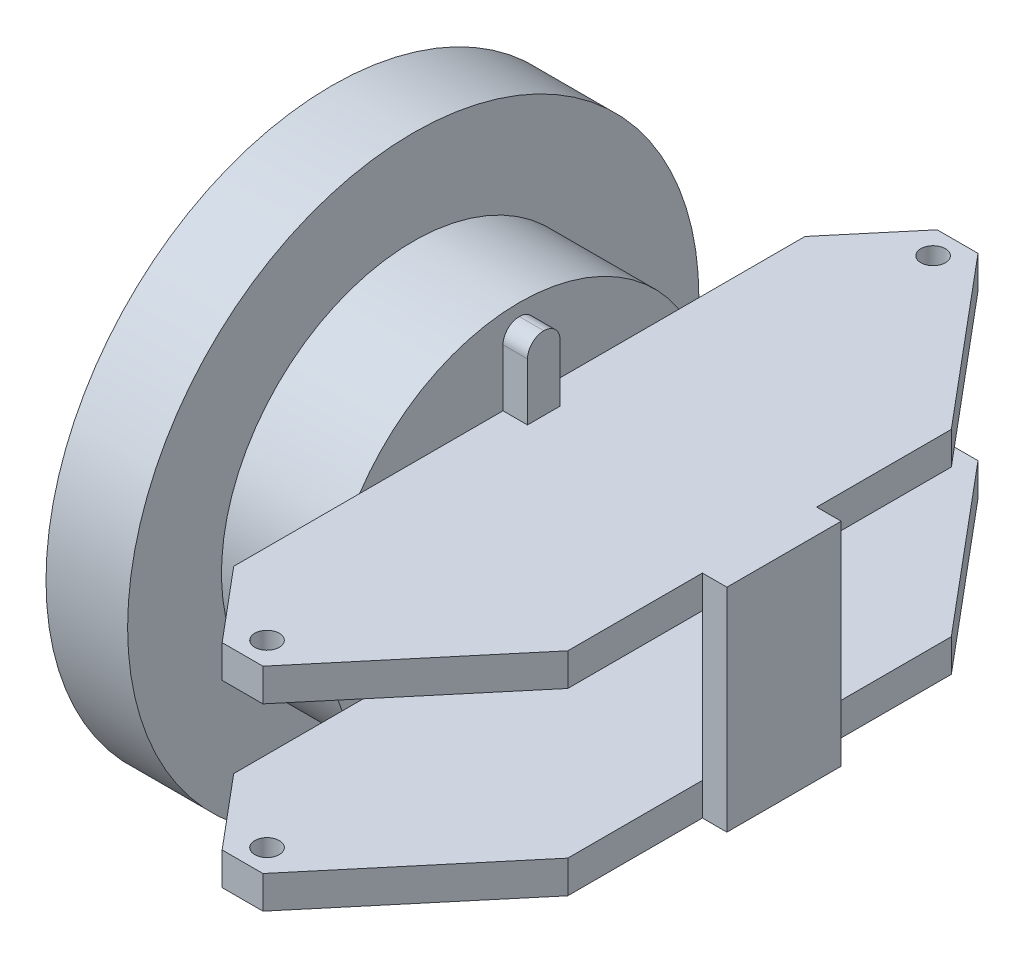
SolidWorks part; units mm, degrees
ref_plane "Front Plane" through (0, 0, 0) normal (0, 0, 1) x (1, 0, 0)
ref_plane "Top Plane" through (0, 0, 0) normal (0, 1, 0) x (1, 0, 0)
ref_plane "Right Plane" through (0, 0, 0) normal (1, 0, 0) x (0, 0, -1)
sketch "Sketch1" plane through (0, 0, 0) normal (1, 0, 0) x (0, 0, -1)
  circle A0 centre (0, 0) radius 35
  dimension "D1" = 70
extrude "Boss-Extrude1" add sketch "Sketch1" along normal blind 10
sketch "Sketch2" plane through (10, 0, 0) normal (1, 0, 0) x (0, 0, -1)
  circle A0 centre (0, 0) radius 23.5
  dimension "D1" = 47
extrude "Boss-Extrude2" add sketch "Sketch2" along normal blind 13
ref_plane "Plane2" through (0, 13, 0) normal (0, 1, 0) x (1, 0, 0)
sketch "Sketch3" plane through (0, 13, 0) normal (0, 1, 0) x (1, 0, 0)
  line L0 (23, 35) -> (23, -35)
  line L1 (23, -23.5) -> (23, 23.5) construction
  line L2 (23, -35) -> (30.3921, -43.8095)
  line L3 (30.3921, -43.8095) -> (35.3921, -43.8095)
  line L4 (35.3921, -43.8095) -> (46.1533, -43.8095) construction
  line L5 (35.3921, -43.8095) -> (52.4338, -23.5)
  line L6 (23, -23.5) -> (77.012, -23.5) construction
  line L7 (52.4338, -23.5) -> (52.4338, 23.5)
  line L8 (23, 0) -> (47.1697, 0) construction
  line L9 (30.3921, 43.8095) -> (35.3921, 43.8095)
  line L10 (23, 35) -> (30.3921, 43.8095)
  line L11 (35.3921, 43.8095) -> (52.4338, 23.5)
  line L12 (10, -23.5) -> (23, -23.5) construction
  point P16 (52.4338, 0)
  dimension "D1" = 35
  dimension "D2" = 11.5
  dimension "D3" = 40
  dimension "D4" = 5
  dimension "D5" = 50
extrude "Boss-Extrude3" add sketch "Sketch3" against normal blind 4
sketch "Sketch4" plane through (0, 13, 0) normal (0, 1, 0) x (1, 0, 0)
  line L0 (30.3921, -43.8095) -> (35.3921, -43.8095) construction
  circle A0 centre (32.8921, -40.8095) radius 1.5
  point P4 (32.8921, -43.8095)
  dimension "D1" = 3
  dimension "D2" = 3
extrude "Cut-Extrude1" cut sketch "Sketch4" against normal blind 4
mirror "Mirror1" about plane through (0, 0, 0) normal (0, 0, 1) of "Cut-Extrude1"
mirror "Mirror2" about plane through (0, 0, 0) normal (0, 1, 0) of "Mirror1", "Cut-Extrude1", "Boss-Extrude3"
sketch "Sketch5" plane through (23, 0, 0) normal (1, 0, 0) x (0, 0, -1)
  line L0 (0, 13) -> (0, 23.5) construction
  line L1 (19.5768, 13) -> (-19.5768, 13) construction
  line L2 (0, 13) -> (-2, 13)
  line L3 (-23.5, 13) -> (23.5, 13) construction
  line L4 (-2, 13) -> (-2, 22)
  line L5 (-2, 22) -> (2, 22)
  line L6 (2, 22) -> (2, 13)
  line L7 (2, 13) -> (0, 13)
  arc A0 (19.5768, 13) -> (-19.5768, 13) centre (0, 0) ccw construction
  dimension "D1" = 9
  dimension "D2" = 2
  dimension "D3" = 2
extrude "Boss-Extrude4" add sketch "Sketch5" along normal blind 3
fillet "Fillet1" radius 2 2 edges at (24.5, 22, 2) (24.5, 22, -2)
mirror "Mirror3" about plane through (0, 0, 0) normal (0, 1, 0) of "Fillet1", "Boss-Extrude4"
sketch "Sketch6" plane through (52.4338, 0, 0) normal (1, 0, 0) x (0, 0, -1)
  line L1 (-7, 13) -> (7, 13)
  line L2 (-7, 13) -> (-7, -13)
  line L3 (-7, -13) -> (7, -13)
  line L4 (7, 13) -> (7, -13)
  line L5 (-7, 13) -> (7, -13) construction
  line L6 (-7, -13) -> (7, 13) construction
  point P0 (0, 0)
  dimension "D1" = 14
  dimension "D2" = 26
extrude "Boss-Extrude5" add sketch "Sketch6" along normal blind 3
sketch "Sketch7" plane through (0, 0, 0) normal (-1, 0, 0) x (0, 0, 1)
  circle A0 centre (0, 0) radius 10
  dimension "D1" = 20
extrude "Cut-Extrude2" cut sketch "Sketch7" against normal blind 10
